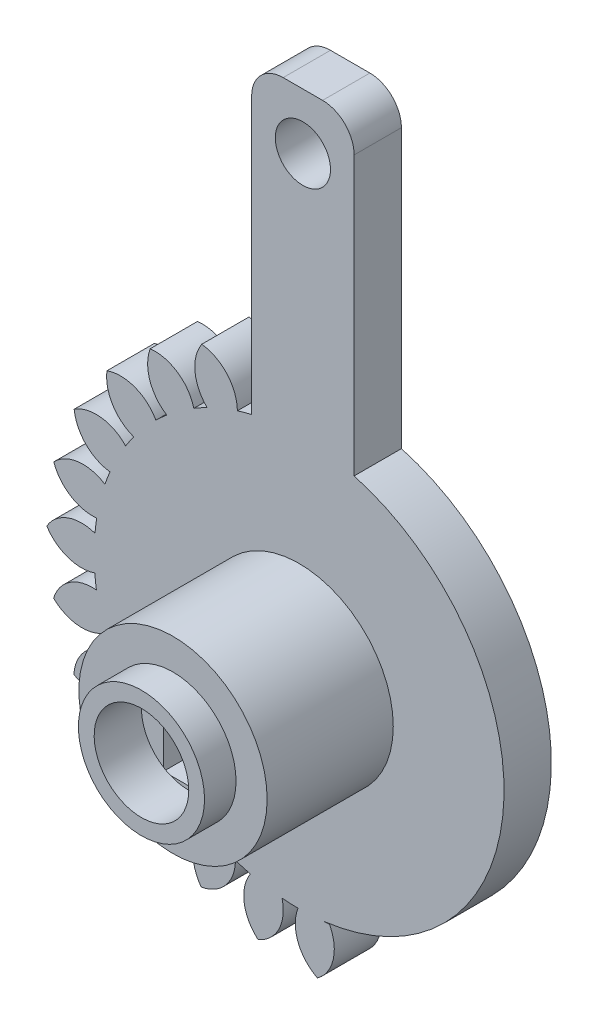
SolidWorks part; units mm, degrees
ref_plane "Front Plane" through (0, 0, 0) normal (0, 0, 1) x (1, 0, 0)
ref_plane "Top Plane" through (0, 0, 0) normal (0, 1, 0) x (1, 0, 0)
ref_plane "Right Plane" through (0, 0, 0) normal (1, 0, 0) x (0, 0, -1)
ref_plane "Plane1" through (0, 0, 5) normal (0, 0, 1) x (1, 0, 0)
ref_plane "Plane2" through (0, 0, 8) normal (0, 0, 1) x (1, 0, 0)
ref_plane "Plane3" through (0, 0, 3) normal (0, 0, 1) x (1, 0, 0)
sketch "Sketch1" plane through (0, 0, 5) normal (0, 0, 1) x (1, 0, 0)
  circle A0 centre (0, 20.9252) radius 3.9726
  circle A1 centre (0, 20.9252) radius 5
  dimension "D1" = 10
sketch "Sketch3" plane through (0, 0, 8) normal (0, 0, 1) x (1, 0, 0)
  line L0 (-3.9726, 20.9252) -> (15.3734, 20.9252) construction
  line L1 (0, 24.8978) -> (0, 8.7425) construction
  line L3 (-1.6, 23.6752) -> (1.6, 23.6752)
  line L4 (-1.6, 23.6752) -> (-1.6, 18.1752)
  line L5 (-1.6, 18.1752) -> (1.6, 18.1752)
  line L6 (1.6, 23.6752) -> (1.6, 18.1752)
  dimension "D1" = 3.2
  dimension "D2" = 5.5
  dimension "D3" = 1.6
  dimension "D4" = 2.75
extrude "Boss-Extrude1" add sketch "Sketch1" along normal blind 9 contours A0
shell "Shell1" thickness 2 removed face at (3.9726, 20.9252, 14) outward yes
extrude "Boss-Extrude2" add sketch "Sketch3" along normal blind 5 separate body
shell "Shell2" thickness 1.5 removed face at (0, 20.9252, 13) outward yes
sketch "Sketch7" plane through (0, 0, 3) normal (0, 0, -1) x (-1, 0, 0)
  line L0 (0, 14.9526) -> (0, 35.2199) construction
  line L1 (5.9726, 20.9252) -> (-26.894, 20.9252) construction
  circle A0 centre (0, 20.9252) radius 5.9726 construction
sketch "Sketch5" plane through (0, 0, 3) normal (0, 0, 1) x (1, 0, 0)
  line L1 (0, 14.9526) -> (0, 35.2199) construction
  line L2 (-5.9726, 20.9252) -> (26.894, 20.9252) construction
  circle A0 centre (0, 20.9252) radius 13
extrude "Boss-Extrude3" add sketch "Sketch5" along normal blind 3 contours A0
sketch "Sketch6" plane through (0, 0, 3) normal (0, 0, 1) x (1, 0, 0)
  line L1 (-3.01, 33.0817) -> (3.49, 33.0817)
  line L2 (-3.01, 33.0817) -> (-3.01, 53.0817)
  line L3 (-3.01, 53.0817) -> (3.49, 53.0817)
  line L4 (3.49, 33.0817) -> (3.49, 53.0817)
  dimension "D1" = 20
  dimension "D2" = 6.5
extrude "Boss-Extrude4" add sketch "Sketch6" along normal up to surface (3 mm away) up to face at (5.9726, 20.9252, 6)
sketch "Sketch8" plane through (0, 0, 3) normal (0, 0, 1) x (1, 0, 0)
  line L0 (-5.7594, 32.4645) -> (-3.9194, 33.1775)
  line L1 (0.24, 53.0817) -> (0.24, -3.388) construction
  line L2 (3.49, 53.0817) -> (-3.01, 53.0817) construction
  line L3 (13, 20.9252) -> (-7.0281, 20.9252) construction
  line L20 (-8.2588, 30.7699) -> (-6.6328, 31.8881)
  line L21 (-10.3, 28.5446) -> (-8.9758, 30.0076)
  line L22 (-11.7731, 25.9085) -> (-10.8219, 27.6375)
  line L23 (-12.5985, 23.0038) -> (-12.0717, 24.9055)
  line L24 (-12.7318, 19.987) -> (-12.6577, 21.9589)
  line L25 (-12.1657, 17.0208) -> (-12.5485, 18.9567)
  line L26 (-10.9309, 14.2651) -> (-11.7498, 16.0605)
  line L27 (-9.0939, 11.8684) -> (-10.3047, 13.4266)
  line L28 (-6.7536, 9.96) -> (-8.2911, 11.197)
  line L29 (-4.0364, 8.6427) -> (-5.8177, 9.4918)
  line L30 (-1.0886, 7.9876) -> (-3.0177, 8.403)
  line L31 (1.9309, 8.03) -> (-0.042, 7.9892)
  arc A0 (-3.9194, 33.1775) -> (-6.1748, 35.8519) centre (-6.4822, 33.3045) ccw
  arc A3 (-6.1748, 35.8519) -> (-5.7594, 32.4645) centre (-4.0035, 34.399) ccw
  arc A4 (-3.01, 33.572) -> (3.49, 33.448) centre (0, 20.9252) ccw construction
  arc A53 (-6.6328, 31.8881) -> (-9.4442, 33.9702) centre (-9.1558, 31.4205) ccw
  arc A54 (-9.4442, 33.9702) -> (-8.2588, 30.7699) centre (-6.9964, 33.0572) ccw
  arc A55 (-8.9758, 30.0076) -> (-12.1916, 31.3853) centre (-11.323, 28.9708) ccw
  arc A56 (-12.1916, 31.3853) -> (-10.3, 28.5446) centre (-9.5992, 31.0614) ccw
  arc A57 (-10.8219, 27.6375) -> (-14.2687, 28.2364) centre (-12.8667, 26.0873) ccw
  arc A58 (-14.2687, 28.2364) -> (-11.7731, 25.9085) centre (-11.6715, 28.5191) ccw
  arc A59 (-12.0717, 24.9055) -> (-15.5637, 24.6934) centre (-13.7039, 22.9256) ccw
  arc A60 (-15.5637, 24.6934) -> (-12.5985, 23.0038) centre (-13.1017, 25.5674) ccw
  arc A61 (-12.6577, 21.9589) -> (-16.0067, 20.9472) centre (-13.7893, 19.656) ccw
  arc A62 (-16.0067, 20.9472) -> (-12.7318, 19.987) centre (-13.8126, 22.3655) ccw
  arc A63 (-12.5485, 18.9567) -> (-15.5739, 17.1999) centre (-13.1185, 16.4548) ccw
  arc A64 (-15.5739, 17.1999) -> (-12.1657, 17.0208) centre (-13.766, 19.0859) ccw
  arc A65 (-11.7498, 16.0605) -> (-14.2885, 13.6534) centre (-11.7274, 13.4946) ccw
  arc A66 (-14.2885, 13.6534) -> (-10.9309, 14.2651) centre (-12.9643, 15.9055) ccw
  arc A67 (-10.3047, 13.4266) -> (-12.2199, 10.4989) centre (-9.6912, 10.9351) ccw
  arc A68 (-12.2199, 10.4989) -> (-9.0939, 11.8684) centre (-11.4507, 12.9957) ccw
  arc A69 (-8.2911, 11.197) -> (-9.4795, 7.9065) centre (-7.1197, 8.9141) ccw
  arc A70 (-9.4795, 7.9065) -> (-6.7536, 9.96) centre (-9.3069, 10.5134) ccw
  arc A71 (-5.8177, 9.4918) -> (-6.2152, 6.016) centre (-4.1513, 7.5406) ccw
  arc A72 (-6.2152, 6.016) -> (-4.0364, 8.6427) centre (-6.6484, 8.5924) ccw
  arc A73 (-3.0177, 8.403) -> (-2.6029, 4.9292) centre (-0.9462, 6.8887) ccw
  arc A74 (-2.6029, 4.9292) -> (-1.0886, 7.9876) centre (-3.6186, 7.3362) ccw
  arc A75 (-0.042, 7.9892) -> (1.1627, 4.7047) centre (2.3228, 6.9935) ccw
  arc A76 (1.1627, 4.7047) -> (1.9309, 8.03) centre (-0.3808, 6.8127) ccw
  point P26 (0.24, 20.9252)
  point P78 (0.24, 20.9252)
  point P153 (0.24, 20.9252)
  dimension "D1" = 13
extrude "Boss-Extrude5" add sketch "Sketch8" along normal up to surface (3 mm away) up to face at (3.9726, 20.9252, 6)
sketch "Sketch9" plane through (0, 0, 3) normal (0, 0, -1) x (-1, 0, 0)
  line L0 (-0.24, 53.0817) -> (-0.24, 49.0919) construction
  line L1 (-3.49, 53.0817) -> (3.01, 53.0817) construction
  circle A0 centre (-0.24, 49.5317) radius 1.75
  dimension "D1" = 3.55
extrude "Cut-Extrude1" cut sketch "Sketch9" against normal up to surface (3 mm away) up to face at (3.9726, 20.9252, 6)
fillet "Fillet1" radius 2 2 edges at (3.49, 53.0817, 4.5) (-3.01, 53.0817, 4.5)
sketch "Sketch11" plane through (0, 0, 13) normal (0, 0, 1) x (1, 0, 0)
  circle A0 centre (0, 20.9354) radius 3
  circle A1 centre (0, 20.9354) radius 4
  dimension "D1" = 6
  dimension "D2" = 8
extrude "Boss-Extrude7" add sketch "Sketch11" along normal blind 3
